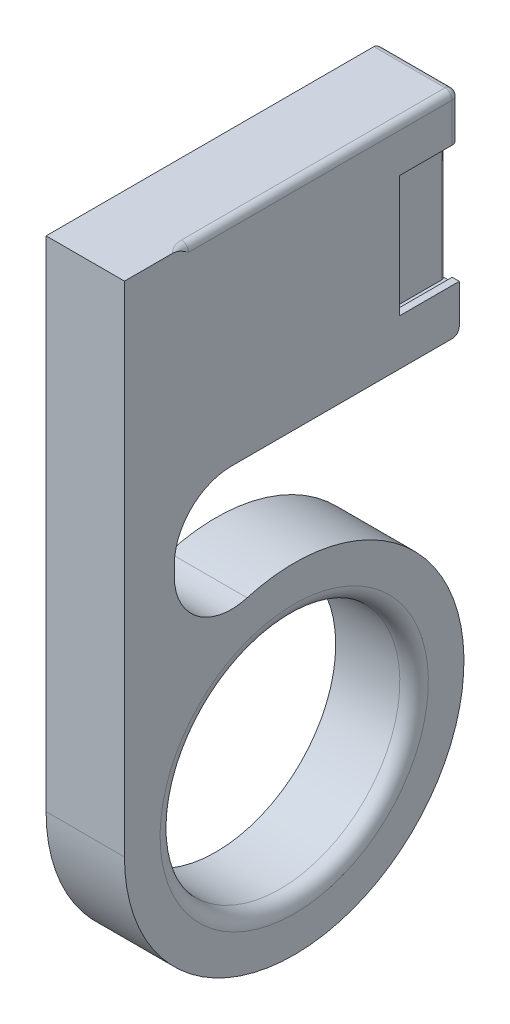
SolidWorks part; units mm, degrees
ref_plane "Front Plane" through (0, 0, 0) normal (0, 0, 1) x (1, 0, 0)
ref_plane "Top Plane" through (0, 0, 0) normal (0, 1, 0) x (1, 0, 0)
ref_plane "Right Plane" through (0, 0, 0) normal (1, 0, 0) x (0, 0, -1)
sketch "Sketch1" plane through (0, 0, 0) normal (1, 0, 0) x (0, 0, -1)
  circle A0 centre (0, 0) radius 16.8275
  circle A1 centre (0, 0) radius 23.8275
  dimension "D1" = 33.655
  dimension "D2" = 7
extrude "Boss-Extrude1" add sketch "Sketch1" along normal blind 25 contours A1 | A0
sketch "Sketch2" plane through (0, 0, 0) normal (0, 1, 0) x (1, 0, 0)
  line L0 (25, -23.8275) -> (25, 23.8275) construction
  line L1 (0, -23.8275) -> (25, -23.8275)
  line L2 (0, -23.8275) -> (0, -16.8275)
  line L3 (0, -16.8275) -> (25, -16.8275)
  line L4 (25, -23.8275) -> (25, -16.8275)
  line L5 (25, -16.8275) -> (25, 16.8275) construction
extrude "Boss-Extrude2" add sketch "Sketch2" along normal blind 70
sketch "Sketch3" plane through (0, 0, 16.8275) normal (0, 0, -1) x (-1, 0, 0)
  line L1 (0, 70) -> (-11, 70)
  line L2 (0, 70) -> (0, 40)
  line L3 (0, 40) -> (-11, 40)
  line L4 (-11, 70) -> (-11, 40)
  dimension "D1" = 11
  dimension "D2" = 30
extrude "Boss-Extrude3" add sketch "Sketch3" along normal blind 40
sketch "Sketch4" plane through (11, 0, 0) normal (1, 0, 0) x (0, 0, -1)
  line L0 (23.1725, 70) -> (23.1725, 40) construction
  line L1 (23.1725, 55) -> (-16.8275, 55)
  line L2 (-16.8275, 70) -> (-16.8275, 40) construction
  line L4 (14.7725, 63.525) -> (23.1725, 63.525)
  line L5 (14.7725, 63.525) -> (14.7725, 46.475)
  line L6 (14.7725, 46.475) -> (23.1725, 46.475)
  line L7 (23.1725, 63.525) -> (23.1725, 46.475)
  line L8 (14.7725, 63.525) -> (23.1725, 46.475) construction
  line L9 (14.7725, 46.475) -> (23.1725, 63.525) construction
  point P8 (18.9725, 55)
  line M8 (23.1725, 40) -> (23.1725, 70)
  dimension "D1" = 17.05
  dimension "D2" = 8.4
extrude "Cut-Extrude1" cut sketch "Sketch4" against normal blind 1 contours L5 L6 L1 M8 | L4 L5 L1 M8 region at (11, 50.7375, -18.9725) region at (11, 59.2625, -18.9725)
sketch "Sketch5" plane through (10, 0, 0) normal (1, 0, 0) x (0, 0, -1)
  line L0 (23.1725, 63.525) -> (23.1725, 46.475) construction
  line L1 (23.1725, 55) -> (14.7725, 55) construction
  line L2 (14.7725, 63.525) -> (14.7725, 46.475) construction
  line L4 (14.1725, 64.125) -> (23.1725, 64.125)
  line L5 (14.1725, 64.125) -> (14.1725, 45.875)
  line L6 (14.1725, 45.875) -> (23.1725, 45.875)
  line L7 (23.1725, 64.125) -> (23.1725, 45.875)
  line L8 (14.1725, 64.125) -> (23.1725, 45.875) construction
  line L9 (14.1725, 45.875) -> (23.1725, 64.125) construction
  point P8 (18.6725, 55)
  dimension "D1" = 18.25
  dimension "D2" = 9
extrude "Cut-Extrude2" cut sketch "Sketch5" against normal blind 1
fillet "Fillet1" radius 0.5 1 edges at (9, 55, -23.1725)
fillet "Fillet2" radius 1 3 edges at (5.5, 40, -23.1725) (0, 55, -23.1725) (5.5, 70, -23.1725)
fillet "Fillet4" radius 2 1 edges at (11, 55, 16.8275)
fillet "Fillet6" radius 1 6 edges at (11, 66.2625, -23.1725) (11, 69.7071, -22.8796) (11, 70, -3.6725) (11.5858, 70, 16.2417) (19, 70, 16.8275) (25, 43.4348, 16.8275)
ref_plane "Plane1" through (11, 0, 0) normal (1, 0, 0) x (0, 0, -1)
sketch "Sketch6" plane through (11, 0, 0) normal (1, 0, 0) x (0, 0, -1)
  line L1 (32.0091, -28.503) -> (-32.3422, -28.503)
  line L2 (32.0091, -28.503) -> (32.0091, 75.2131)
  line L3 (32.0091, 75.2131) -> (-32.3422, 75.2131)
  line L4 (-32.3422, -28.503) -> (-32.3422, 75.2131)
extrude "Cut-Extrude3" cut sketch "Sketch6" along normal through all
fillet "Fillet7" radius 8 2 edges at (5.5, 16.8696, 16.8275) (5.5, 40, 16.8275)
fillet "Fillet8" radius 2 1 edges at (11, 16.8275, 0)
